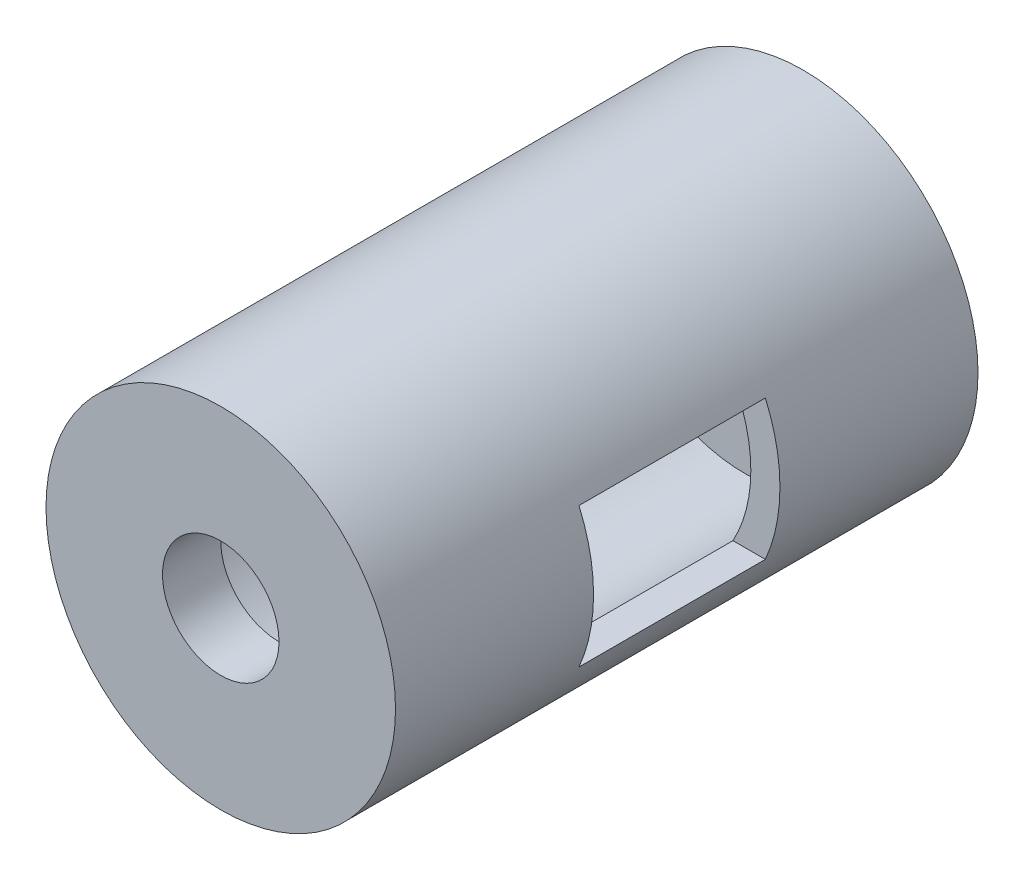
SolidWorks part; units mm, degrees
ref_plane "Front Plane" through (0, 0, 0) normal (0, 0, 1) x (1, 0, 0)
ref_plane "Top Plane" through (0, 0, 0) normal (0, 1, 0) x (1, 0, 0)
ref_plane "Right Plane" through (0, 0, 0) normal (1, 0, 0) x (0, 0, -1)
sketch "Sketch1" plane through (0, 0, 0) normal (0, 0, 1) x (1, 0, 0)
  circle A0 centre (3.864, -0.112) radius 12.5
  circle A1 centre (3.864, -0.112) radius 15
  dimension "D1" = 25
  dimension "D2" = 30
extrude "Boss-Extrude1" add sketch "Sketch1" along normal blind 40
sketch "Sketch2" plane through (0, 0, 40) normal (0, 0, 1) x (1, 0, 0)
  circle A0 centre (3.864, -0.112) radius 15
  dimension "D1" = 30
extrude "Boss-Extrude2" add sketch "Sketch2" along normal blind 5
sketch "Sketch3" plane through (0, 0, 0) normal (0, 0, -1) x (-1, 0, 0)
  circle A0 centre (-3.864, -0.112) radius 15
  dimension "D1" = 30
extrude "Boss-Extrude3" add sketch "Sketch3" along normal blind 5
sketch "Sketch4" plane through (0, 0, -5) normal (0, 0, -1) x (-1, 0, 0)
  circle A0 centre (-3.864, -0.112) radius 5
  dimension "D1" = 10
extrude "Boss-Extrude4" add sketch "Sketch4" against normal blind 160 separate body
combine bodies "Combine1" operation type subtract main body 109 bodies to subtract 110
ref_axis "Axis1" through (3.864, -0.112, 45) along (0, 0, -1)
sketch "Sketch5" plane through (0, 0, 0) normal (1, 0, 0) x (0, 0, -1)
  line L6 (-12, 5.888) -> (-28, 5.888)
  line L7 (-12, 5.888) -> (-12, -6.112)
  line L8 (-12, -6.112) -> (-28, -6.112)
  line L9 (-28, 5.888) -> (-28, -6.112)
  dimension "D3" = 12
  dimension "D4" = 16
extrude "Cut-Extrude1" cut sketch "Sketch5" along normal blind 160
